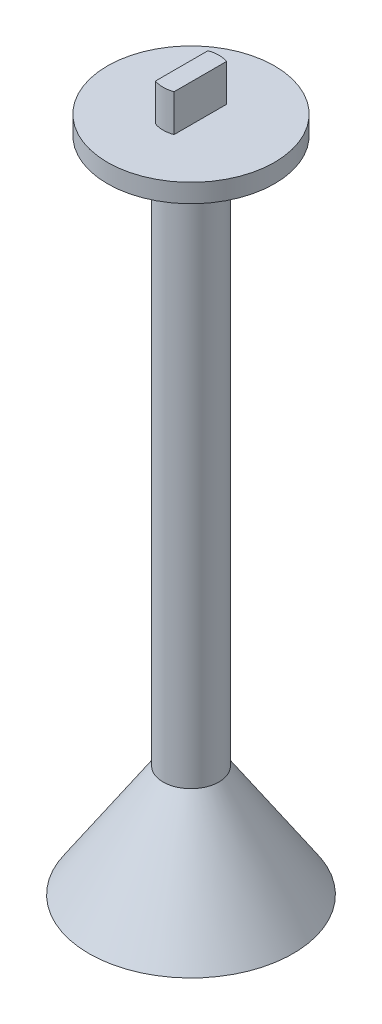
SolidWorks part; units mm, degrees
material "1023 Carbon Steel Sheet (SS)"
ref_plane "Front Plane" through (0, 0, 0) normal (0, 0, 1) x (1, 0, 0)
ref_plane "Top Plane" through (0, 0, 0) normal (0, 1, 0) x (1, 0, 0)
ref_plane "Right Plane" through (0, 0, 0) normal (1, 0, 0) x (0, 0, -1)
sketch "Sketch1" plane through (0, 0, 0) normal (0, 1, 0) x (1, 0, 0)
  circle A0 centre (0, 0) radius 27.5
  dimension "D1" = 55
ref_plane "Plane1" through (0, 30, 0) normal (0, 1, 0) x (1, 0, 0)
sketch "Sketch2" plane through (0, 30, 0) normal (0, 1, 0) x (1, 0, 0)
  circle A0 centre (0, 0) radius 7.5
  dimension "D1" = 15
loft "Loft1" add profiles "Sketch2", "Sketch1" connector at (-0.0141, 30, 7.5) connector at (-0.0173, 0, 27.5)
extrude "Boss-Extrude1" add sketch "Sketch2<2>" along normal blind 162
sketch "Sketch2<2>" plane through (0, 30, 0) normal (0, 1, 0) x (1, 0, 0) same geometry as "Sketch2"
ref_plane "Plane2" through (0, 177, 0) normal (0, 1, 0) x (1, 0, 0)
sketch "Sketch3" plane through (0, 177, 0) normal (0, 1, 0) x (1, 0, 0)
  circle A0 centre (0, 0) radius 22.5
  dimension "D1" = 45
extrude "Boss-Extrude2" add sketch "Sketch3" along normal blind 5
sketch "Sketch5" plane through (0, 192, 0) normal (0, 1, 0) x (1, 0, 0)
  line L2 (0, 0) -> (0, -15.7411) construction
  line L3 (2.5, 7.0711) -> (2.5, -7.0711)
  line L4 (-2.5, 7.0711) -> (-2.5, -7.0711)
  arc A0 (0, -7.5) -> (2.5, 7.0711) centre (0, 0) ccw
  circle A4 centre (0, 0) radius 7.5 construction
  circle A5 centre (0, 0) radius 7.5 construction
  arc A6 (-2.5, 7.0711) -> (-2.5, -7.0711) centre (0, 0) ccw
  circle M4 centre (0, 0) radius 7.5
  dimension "D1" = 2.5
extrude "Cut-Extrude3" cut sketch "Sketch5" against normal blind 10 contours L3 M4 | L4 M4 region at (4.5711, 192, 0) region at (-4.5711, 192, 0)
sketch "Sketch21" plane through (0, 0, 0) normal (0, -1, 0) x (1, 0, 0)
  circle A0 centre (0, 0) radius 5
  dimension "D1" = 10
extrude "Cut-Extrude4" cut sketch "Sketch21" against normal blind 20
